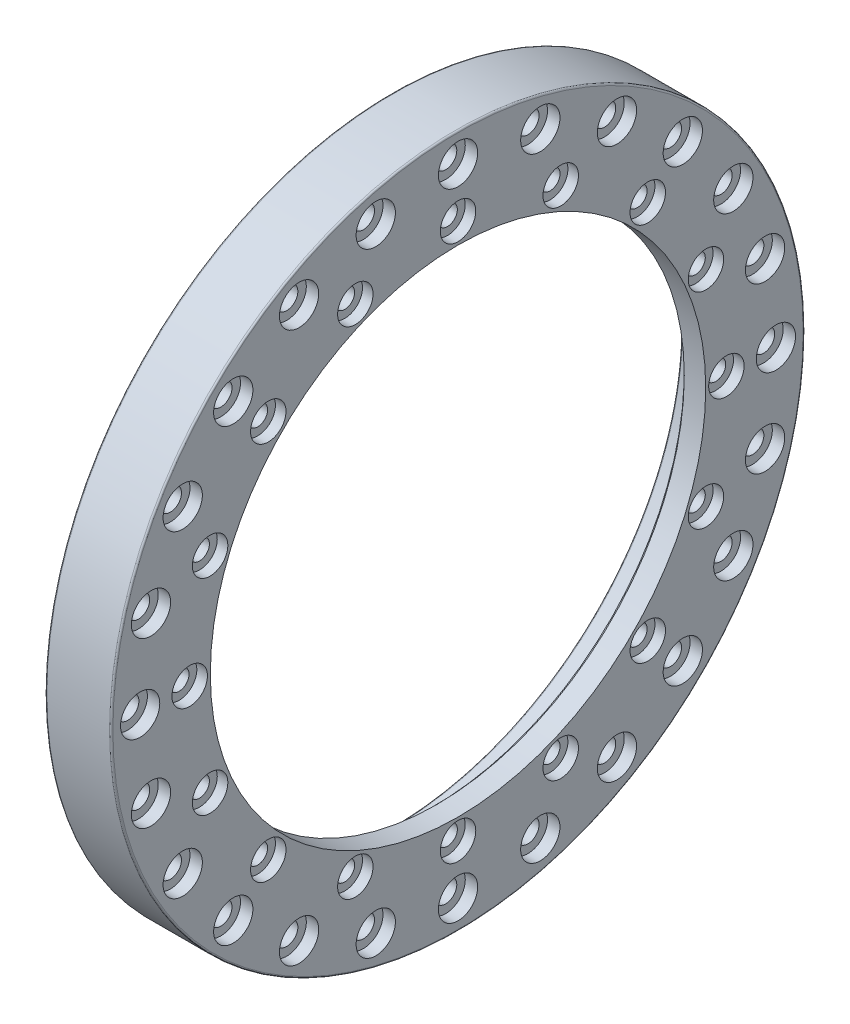
SolidWorks part; units mm, degrees
ref_plane "Front Plane" through (0, 0, 0) normal (0, 0, 1) x (1, 0, 0)
ref_plane "Top Plane" through (0, 0, 0) normal (0, 1, 0) x (1, 0, 0)
ref_plane "Right Plane" through (0, 0, 0) normal (1, 0, 0) x (0, 0, -1)
sketch "Sketch1" plane through (0, 0, 0) normal (0, 0, 1) x (1, 0, 0)
  line L0 (0, 0) -> (0, 210) construction
  line L1 (-20, 210) -> (20, 210)
  line L2 (20, 210) -> (20, 150)
  line L3 (20, 150) -> (5, 150)
  line L4 (5, 150) -> (5, 175)
  line L5 (5, 175) -> (-20, 175)
  line L6 (-20, 175) -> (-20, 210)
  line L7 (0, 0) -> (-34.0692, 0) construction
  dimension "D1" = 40
  dimension "D2" = 15
  dimension "D3" = 210
  dimension "D4" = 150
  dimension "D5" = 175
revolve "Revolve1" add sketch "Sketch1" angle 360 about L7
ref_axis "Axis1" through (-20, 0, 0) along (1, 0, 0)
sketch "Sketch11" plane through (20, 0, 0) normal (1, 0, 0) x (0, 0, -1)
  line L0 (0, 210) -> (0, 175) construction
  line L1 (0, 175) -> (0, 150) construction
  circle A0 centre (0, 0) radius 210 construction
  circle A1 centre (0, 0) radius 175 construction
  circle A2 centre (0, 0) radius 150 construction
  point P7 (0, 192.5)
  point P12 (0, 162.5)
hole_wizard "CBORE for M12 Hex Head Bolt3" positions "3DSketch7" profile "Sketch13" counterbore size "M12" standard "ISO" end condition through all
sketch3d "3DSketch7"
  point P0 (20, 192.5, 0)
sketch "Sketch13" plane through (20, 192.5, 0) normal (0, 1, 0) x (0, 0, -1)
  line L0 (0, 0) -> (0, 40)
  line L1 (0, 40) -> (6.75, 40)
  line L3 (6.75, 40) -> (6.75, 7.5)
  line L4 (6.75, 7.5) -> (11.8925, 7.5)
  line L5 (11.8925, 7.5) -> (11.8925, 0)
  line L7 (11.8925, 0) -> (0, 0)
  line L11 (0, -6.35) -> (0, 107.95) construction
  dimension "Thru Hole Dia." = 13.5
  dimension "Thru Hole Depth" = 40
  dimension "C'Bore Dia." = 23.785
  dimension "C'Bore Depth" = 7.5
pattern_circular "CirPattern1" count 24 over 360 about axis through (-20, 0, 0) along (1, 0, 0) of "CBORE for M12 Hex Head Bolt3"
fillet "Fillet1" radius 1 3 edges at (-20, 0, -175) (20, 0, -210) (-20, 0, -210)
chamfer "Chamfer1" distance 2 angle 45 1 edges at (5, 0, -150)
hole_wizard "CBORE for M10 Hex Head Bolt1" positions "3DSketch8" profile "Sketch16" counterbore size "M10" standard "ISO" end condition through all
sketch3d "3DSketch8"
  point P0 (20, 162.5, 0)
sketch "Sketch16" plane through (20, 162.5, 0) normal (0, 1, 0) x (0, 0, -1)
  line L0 (0, 0) -> (0, 40)
  line L1 (0, 40) -> (6, 40)
  line L3 (6, 40) -> (6, 6.4)
  line L4 (6, 6.4) -> (10.7375, 6.4)
  line L5 (10.7375, 6.4) -> (10.7375, 0)
  line L7 (10.7375, 0) -> (0, 0)
  line L11 (0, -6.35) -> (0, 107.95) construction
  dimension "Thru Hole Dia." = 12
  dimension "Thru Hole Depth" = 40
  dimension "C'Bore Dia." = 21.475
  dimension "C'Bore Depth" = 6.4
pattern_circular "CirPattern2" count 16 over 360 about axis through (-20, 0, 0) along (1, 0, 0) of "CBORE for M10 Hex Head Bolt1"
